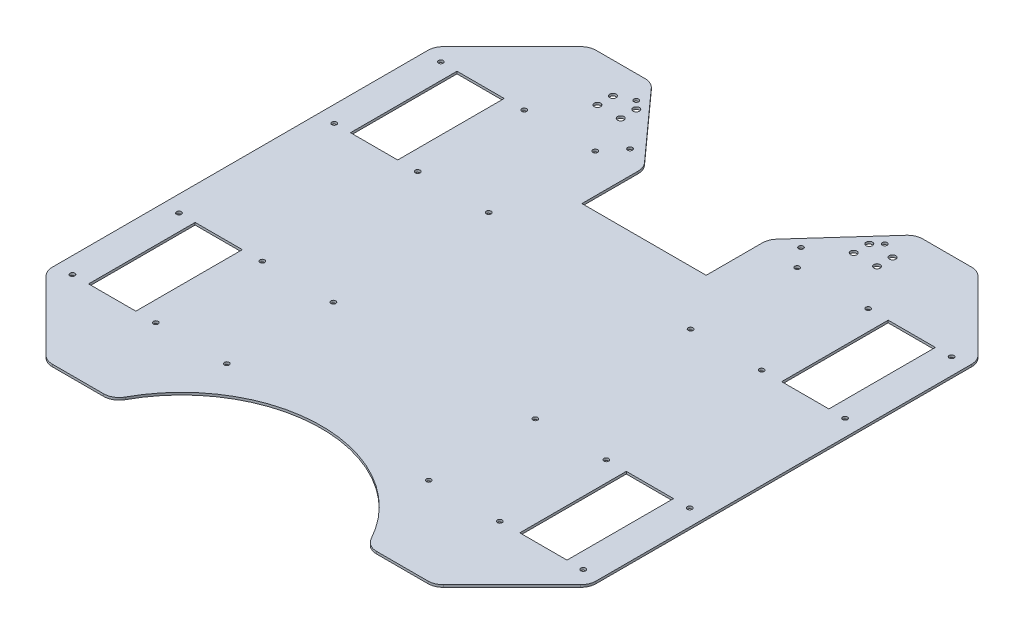
SolidWorks part; units mm, degrees
material "PMMA"
ref_plane "前视基准面" through (0, 0, 0) normal (0, 0, 1) x (1, 0, 0)
ref_plane "上视基准面" through (0, 0, 0) normal (0, 1, 0) x (1, 0, 0)
ref_plane "右视基准面" through (0, 0, 0) normal (1, 0, 0) x (0, 0, -1)
other "Configuration Table"
sketch "草图1" plane through (0, 0, 0) normal (0, 1, 0) x (1, 0, 0)
  line L0 (-125, 175) -> (-175, 125)
  line L1 (125, -175) -> (81.7103, -175)
  line L2 (175, -125) -> (175, 125)
  line L3 (125, 175) -> (85, 175)
  line L4 (-175, -125) -> (-175, 125)
  line L5 (-85, 175) -> (-40, 125)
  line L7 (125, 175) -> (175, 125)
  line L8 (175, -125) -> (125, -175)
  line L9 (-125, -175) -> (-175, -125)
  line L10 (40, 125) -> (85, 175)
  line L11 (-85, 175) -> (-125, 175)
  line L12 (40, 125) -> (40, 85)
  line L13 (40, 85) -> (-40, 85)
  line L14 (-40, 85) -> (-40, 125)
  line L15 (-153.994, 50) -> (-123.594, 50)
  line L16 (-123.594, 50) -> (-123.594, 118.58)
  line L17 (-123.594, 118.58) -> (-153.994, 118.58)
  line L18 (-153.994, 118.58) -> (-153.994, 50)
  line L19 (123.594, 50) -> (153.994, 50)
  line L20 (153.994, 50) -> (153.994, 118.58)
  line L21 (153.994, 118.58) -> (123.594, 118.58)
  line L22 (123.594, 118.58) -> (123.594, 50)
  line L23 (-175, 0) -> (175, 0) construction
  line L24 (-123.594, -118.58) -> (-153.994, -118.58)
  line L25 (-123.594, -50) -> (-123.594, -118.58)
  line L26 (-153.994, -50) -> (-123.594, -50)
  line L27 (-153.994, -118.58) -> (-153.994, -50)
  line L28 (153.994, -118.58) -> (123.594, -118.58)
  line L29 (153.994, -50) -> (153.994, -118.58)
  line L30 (123.594, -50) -> (153.994, -50)
  line L31 (123.594, -118.58) -> (123.594, -50)
  line L32 (-81.7103, -175) -> (-125, -175)
  line L33 (-80, 160) -> (-55, 131) construction
  line L34 (0, 0) -> (0, 46.7243)
  circle A0 centre (-55, 131) radius 1.55
  circle A1 centre (-80, 160) radius 1.55
  circle A2 centre (55, 131) radius 1.55
  circle A3 centre (80, 160) radius 1.55
  circle A4 centre (-65, 118.58) radius 1.55
  circle A5 centre (-65, 50) radius 1.55
  circle A6 centre (-110.72, 50) radius 1.55
  circle A7 centre (-110.72, 118.58) radius 1.55
  circle A12 centre (-164.434, 118.58) radius 1.55
  circle A13 centre (-164.434, 50) radius 1.55
  circle A14 centre (-65, -118.58) radius 1.55
  circle A15 centre (-65, -50) radius 1.55
  circle A16 centre (-110.72, -50) radius 1.55
  circle A17 centre (-110.72, -118.58) radius 1.55
  circle A18 centre (-164.434, -50) radius 1.55
  circle A19 centre (-164.434, -118.58) radius 1.55
  circle A20 centre (65, 50) radius 1.55
  circle A21 centre (110.72, 50) radius 1.55
  circle A22 centre (110.72, 118.58) radius 1.55
  circle A23 centre (65, 118.58) radius 1.55
  circle A24 centre (164.434, 118.58) radius 1.55
  circle A25 centre (164.434, 50) radius 1.55
  circle A26 centre (164.434, -118.58) radius 1.55
  circle A27 centre (164.434, -50) radius 1.55
  circle A28 centre (110.72, -50) radius 1.55
  circle A29 centre (110.72, -118.58) radius 1.55
  circle A30 centre (65, -118.58) radius 1.55
  circle A31 centre (65, -50) radius 1.55
  arc A32 (-81.7103, -175) -> (81.7103, -175) centre (0, -212.7283) cw
  circle A33 centre (-90, 155) radius 2.05
  circle A34 centre (-75, 155) radius 2.05
  circle A35 centre (-90, 145) radius 2.05
  circle A36 centre (-75, 145) radius 2.05
  circle A37 centre (75, 145) radius 2.05
  circle A38 centre (90, 145) radius 2.05
  circle A39 centre (75, 155) radius 2.05
  circle A40 centre (90, 155) radius 2.05
  point P0 (0, 0)
  point P1 (-85, 175)
  point P2 (85, 175)
  point P3 (40, 125)
  point P4 (-40, 125)
  point P6 (125, 175)
  point P8 (175, 125)
  point P10 (175, -125)
  point P11 (125, -175)
  point P12 (-125, -175)
  point P13 (-175, -125)
  point P24 (-80, 160)
  point P25 (-55, 131)
  point P26 (55, 131)
  point P27 (80, 160)
  point P36 (-164.434, 118.58)
  point P37 (-164.434, 50)
  point P38 (-153.994, 118.58)
  point P39 (-123.594, 50)
  point P40 (-110.72, 118.58)
  point P41 (-110.72, 50)
  point P42 (-65, 118.58)
  point P43 (-65, 50)
  point P47 (-123.594, 118.58)
  point P53 (-153.994, 50)
  point P66 (-40, 85)
  point P67 (40, 85)
  point P70 (110.72, 50)
  point P71 (65, 50)
  point P72 (123.594, 50)
  point P73 (153.994, 50)
  point P74 (164.434, 50)
  point P75 (65, 118.58)
  point P76 (110.72, 118.58)
  point P77 (123.594, 118.58)
  point P78 (153.994, 118.58)
  point P81 (164.434, 118.58)
  point P85 (-65, -118.58)
  point P88 (-65, -50)
  point P91 (-110.72, -50)
  point P94 (-110.72, -118.58)
  point P101 (-164.434, -50)
  point P104 (-164.434, -118.58)
  point P118 (164.434, -118.58)
  point P121 (164.434, -50)
  point P128 (110.72, -50)
  point P131 (110.72, -118.58)
  point P134 (65, -118.58)
  point P137 (65, -50)
  point P159 (0, 0)
  point P160 (0, 0)
  dimension "D29" = 3.1
  dimension "D30" = 3.1
  dimension "D31" = 3.1
  dimension "D32" = 3.1
  dimension "D40" = 3.1
  dimension "D41" = 3.1
  dimension "D42" = 3.1
  dimension "D43" = 3.1
  dimension "D44" = 3.1
  dimension "D45" = 3.1
  dimension "D46" = 3.1
  dimension "D47" = 3.1
  dimension "D48" = 3.1
  dimension "D49" = 3.1
  dimension "D60" = 3.1
  dimension "D61" = 3.1
  dimension "D62" = 43.2897
  dimension "D63" = 90
  dimension "D66" = 20
  dimension "D68" = 10
  dimension "D70" = 4.1
  dimension "D71" = 4.1
  dimension "D72" = 4.1
  dimension "D73" = 4.1
  dimension "D74" = 5
  dimension "D1" = 175
  dimension "D2" = 175
  dimension "D3" = 125
  dimension "D4" = 125
  dimension "D5" = 125
  dimension "D6" = 125
  dimension "D7" = 125
  dimension "D8" = 125
  dimension "D9" = 125
  dimension "D10" = 125
  dimension "D11" = 175
  dimension "D12" = 175
  dimension "D13" = 40
  dimension "D14" = 40
  dimension "D15" = 85
  dimension "D16" = 85
  dimension "D17" = 125
  dimension "D18" = 125
  dimension "D19" = 40
  dimension "D20" = 45
  dimension "D21" = 160
  dimension "D22" = 160
  dimension "D23" = 80
  dimension "D24" = 80
  dimension "D25" = 55
  dimension "D26" = 131
  dimension "D27" = 55
  dimension "D28" = 131
  dimension "D33" = 50
  dimension "D34" = 118.58
  dimension "D35" = 65
  dimension "D36" = 45.72
  dimension "D37" = 12.874
  dimension "D38" = 30.4
  dimension "D39" = 10.44
  dimension "D50" = 40
  dimension "D51" = 40
  dimension "D52" = 85
  dimension "D53" = 85
  dimension "D54" = 138.013
  dimension "D55" = 65
  dimension "D56" = 45.72
  dimension "D57" = 12.874
  dimension "D58" = 30.4
  dimension "D59" = 10.44
  dimension "D64" = 0
  dimension "D65" = 25
  dimension "D67" = 15
  dimension "D69" = 35
extrude "凸台-拉伸1" add sketch "草图1" along normal blind 1.5 contours A1 | A0 | L8 L1 A32 L32 L9 L4 L0 L11 L5 L14 L13 L12 L10 L3 L7 L2 | A5 | A3 | A2 | A4 | A7 | A12 | L16 L17 L18 L15 | A6 | L21 L22 L19 L20 | A13 | A16 | A17 | A14 | A15 | A18 | A19 | L25 L24 L27 L26 | A20 | A21 | A22 | A23 | A24 | A25 | A28 | A26 | A27 | L28 L31 L30 L29 | A30 | A31 | A29
fillet "圆角1" radius 10 1 edges at (-40, 0.75, -125)
fillet "圆角2" radius 10 1 edges at (40, 0.75, -125)
fillet "圆角3" radius 10 12 edges at (-85, 0.75, -175) (85, 0.75, -175) (125, 0.75, -175) (175, 0.75, -125) (175, 0.75, 125) (125, 0.75, 175) (81.7103, 0.75, 175) (-81.7103, 0.75, 175) (-125, 0.75, 175) (-175, 0.75, 125) (-175, 0.75, -125) (-125, 0.75, -175)
extrude "切除-拉伸3" cut sketch "草图1<5>" along normal blind 10 contours A40 | A39 | A38 | A37 | A36 | A33 | A35 | A34 region at (-90, 0, -155) region at (-90, 0, -145) region at (-75, 0, -145) region at (75, 0, -145) region at (90, 0, -145) region at (75, 0, -155) region at (90, 0, -155)
sketch "草图1<5>" plane through (0, 0, 0) normal (0, 1, 0) x (1, 0, 0) same geometry as "草图1"
